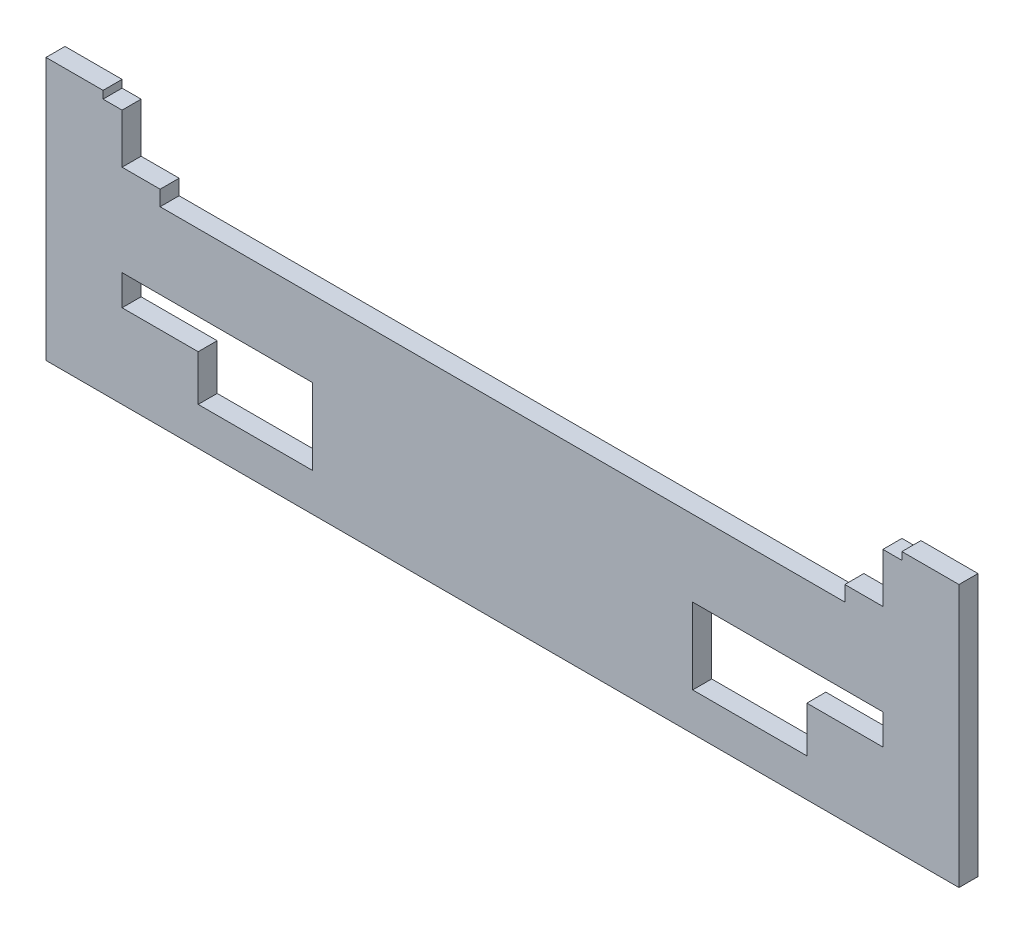
SolidWorks part; units mm, degrees
material "Acrylic (Medium-high impact)"
ref_plane "Front Plane" through (0, 0, 0) normal (0, 0, 1) x (1, 0, 0)
ref_plane "Top Plane" through (0, 0, 0) normal (0, 1, 0) x (1, 0, 0)
ref_plane "Right Plane" through (0, 0, 0) normal (1, 0, 0) x (0, 0, -1)
sketch "Sketch1" plane through (0, 0, 0) normal (0, 0, 1) x (1, 0, 0)
  line L0 (0, 0) -> (240, 0)
  line L1 (220, 54) -> (210, 54)
  line L2 (210, 54) -> (210, 50)
  line L3 (240, 0) -> (240, 69)
  line L4 (30, 50) -> (30, 54)
  line L5 (30, 54) -> (20, 54)
  line L6 (240, 69) -> (225, 69)
  line L7 (225, 69) -> (225, 67)
  line L8 (225, 67) -> (220, 67)
  line L9 (220, 67) -> (220, 54)
  line L10 (210, 50) -> (30, 50)
  line L11 (20, 54) -> (20, 67)
  line L12 (20, 67) -> (15, 67)
  line L13 (15, 67) -> (15, 69)
  line L14 (15, 69) -> (0, 69)
  line L17 (0, 69) -> (0, 0)
  dimension "D1" = 20
  dimension "D2" = 20
  dimension "D3" = 240
  dimension "D4" = 15
  dimension "D5" = 2
  dimension "D6" = 17
  dimension "D7" = 50
  dimension "D8" = 10
  dimension "D9" = 4
extrude "Boss-Extrude1" add sketch "Sketch1" along normal blind 5
sketch "Sketch6" plane through (0, 0, 5) normal (0, 0, 1) x (1, 0, 0)
  line L0 (20, 30) -> (70, 30)
  line L1 (70, 30) -> (70, 10)
  line L2 (70, 10) -> (40, 10)
  line L3 (40, 10) -> (40, 22)
  line L4 (40, 22) -> (20, 22)
  line L5 (20, 22) -> (20, 30)
  line L6 (0, 0) -> (240, 0) construction
  line L7 (0, 69) -> (0, 0) construction
  line L8 (120, 0) -> (120, 50) construction
  line L10 (220, 22) -> (220, 30)
  line L11 (200, 22) -> (220, 22)
  line L12 (200, 10) -> (200, 22)
  line L13 (170, 10) -> (200, 10)
  line L14 (170, 30) -> (170, 10)
  line L15 (220, 30) -> (170, 30)
  line L17 (210, 50) -> (30, 50) construction
  dimension "D1" = 50
  dimension "D2" = 20
  dimension "D3" = 8
  dimension "D4" = 12
  dimension "D5" = 10
  dimension "D6" = 20
extrude "Cut-Extrude5" cut sketch "Sketch6" against normal up to next
